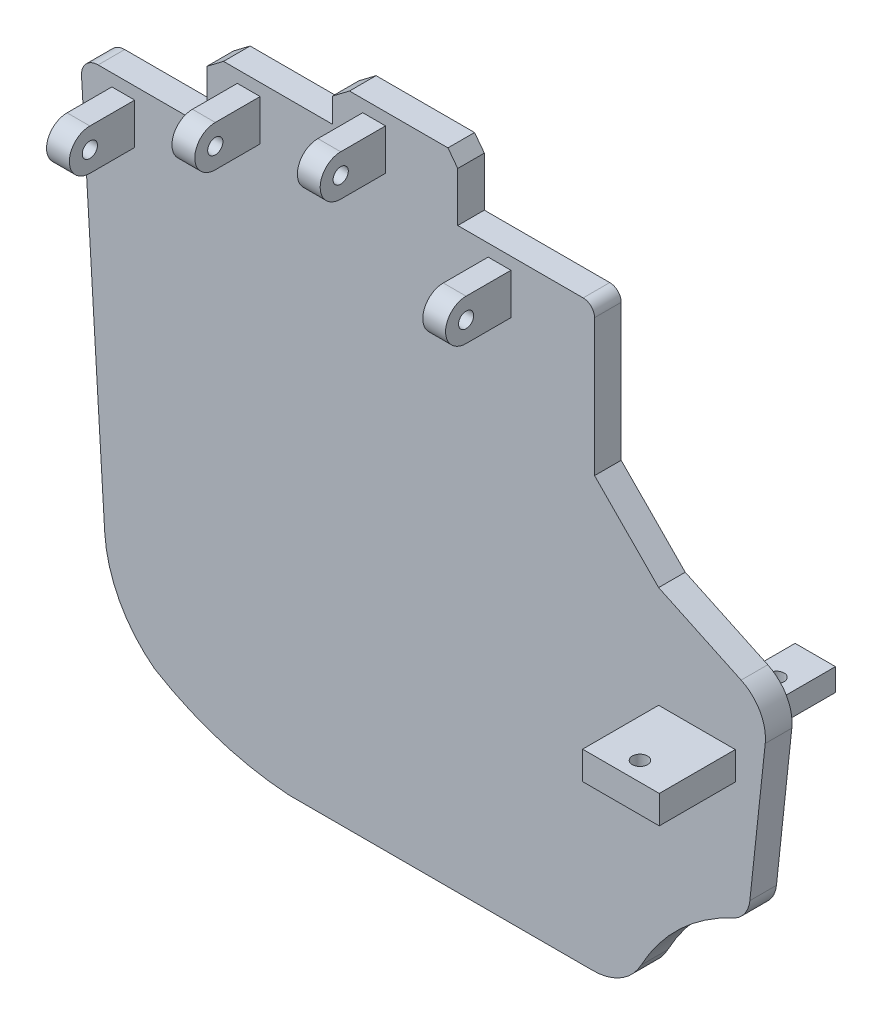
SolidWorks part; units mm, degrees
ref_plane "Front Plane" through (0, 0, 0) normal (0, 0, 1) x (1, 0, 0)
ref_plane "Top Plane" through (0, 0, 0) normal (0, 1, 0) x (1, 0, 0)
ref_plane "Right Plane" through (0, 0, 0) normal (1, 0, 0) x (0, 0, -1)
sketch "Sketch1" plane through (0, 0, 0) normal (0, 0, 1) x (1, 0, 0)
  line L0 (0, 0) -> (40, 0)
  line L1 (60.6551, 18.2857) -> (62.676, 37.2057)
  line L2 (59.5073, 42.8438) -> (48.6521, 47.9589)
  line L3 (48.6521, 47.9589) -> (40.223, 56.5)
  line L4 (40.223, 56.5) -> (40.223, 74.5)
  line L5 (38.723, 76) -> (22.223, 76)
  line L6 (22.223, 76) -> (22.223, 82.5)
  line L7 (22.223, 82.5) -> (20.934, 84.2022)
  line L8 (20.934, 84.2022) -> (7.9777, 84.2022)
  line L9 (7.9777, 84.2022) -> (5.723, 82.4947)
  line L10 (5.723, 82.4947) -> (5.723, 79.2947)
  line L11 (5.723, 79.2947) -> (-8.5938, 79.2947)
  line L12 (-8.5938, 79.2947) -> (-10.777, 77.6413)
  line L13 (-10.777, 77.6413) -> (-10.777, 70.6413)
  line L14 (-10.777, 70.6413) -> (-25.0938, 70.6413)
  line L15 (-27.277, 68.3221) -> (-24.2226, 17.8235)
  arc A0 (40, 0) -> (46.3551, 3.8023) centre (40, 7.2121) ccw
  arc A1 (46.3551, 3.8023) -> (58.452, 15.2105) centre (69.4891, -8.6104) cw
  arc A2 (58.452, 15.2105) -> (60.6551, 18.2857) centre (56.8383, 18.6934) ccw
  arc A3 (62.676, 37.2057) -> (59.5073, 42.8438) centre (57.1298, 37.7981) ccw
  arc A4 (40.223, 74.5) -> (38.723, 76) centre (38.723, 74.5) ccw
  arc A5 (-25.0938, 70.6413) -> (-27.277, 68.3221) centre (-25.0938, 68.4541) ccw
  arc A6 (-24.2226, 17.8235) -> (-17.6447, 5.5352) centre (-7.5746, 18.8305) ccw
  arc A7 (-17.6447, 5.5352) -> (0, 0) centre (2.5612, 39.0552) ccw
  dimension "D1" = 76
  dimension "D2" = 40
  dimension "D3" = 16.5
  dimension "D4" = 7
  dimension "D5" = 18
  dimension "D6" = 6.5
  dimension "D7" = 3.2
  dimension "D8" = 16.5
  dimension "D9" = 16.5
  dimension "D10" = 16.5
  dimension "D11" = 67.5
  dimension "D12" = 12
  dimension "D13" = 12
extrude "Boss-Extrude1" add sketch "Sketch1" along normal blind 3.5
sketch "Sketch2" plane through (0, 0, 3.5) normal (0, 0, 1) x (1, 0, 0)
  line L0 (-23.277, 69.0413) -> (-20.277, 69.0413)
  line L1 (-20.277, 69.0413) -> (-20.277, 63.6413)
  line L2 (-20.277, 63.6413) -> (-23.277, 63.6413)
  line L3 (-23.277, 63.6413) -> (-23.277, 69.0413)
  line L4 (-10.777, 77.6413) -> (-10.777, 70.6413) construction
  line L5 (-10.777, 70.6413) -> (-25.0938, 70.6413) construction
  line L6 (5.723, 79.2947) -> (-8.5938, 79.2947) construction
  line L7 (-6.777, 77.6947) -> (-3.777, 77.6947)
  line L8 (-6.777, 77.6947) -> (-6.777, 72.2947)
  line L9 (-6.777, 72.2947) -> (-3.777, 72.2947)
  line L10 (-3.777, 77.6947) -> (-3.777, 72.2947)
  line L11 (9.723, 82.6022) -> (12.723, 82.6022)
  line L12 (9.723, 82.6022) -> (9.723, 77.2022)
  line L13 (9.723, 77.2022) -> (12.723, 77.2022)
  line L14 (12.723, 82.6022) -> (12.723, 77.2022)
  line L15 (26.223, 74.4) -> (29.223, 74.4)
  line L16 (26.223, 74.4) -> (26.223, 69)
  line L17 (26.223, 69) -> (29.223, 69)
  line L18 (29.223, 74.4) -> (29.223, 69)
  line L19 (20.934, 84.2022) -> (7.9777, 84.2022) construction
  line L20 (38.723, 76) -> (22.223, 76) construction
  line L21 (5.723, 82.4947) -> (5.723, 79.2947) construction
  line L22 (22.223, 76) -> (22.223, 82.5) construction
  point P26 (-3.777, 74.9947)
  dimension "D1" = 3
  dimension "D2" = 5.4
  dimension "D3" = 9.5
  dimension "D4" = 1.6
  dimension "D5" = 1.6
  dimension "D6" = 1.6
  dimension "D7" = 1.6
  dimension "D8" = 9.5
  dimension "D9" = 9.5
  dimension "D10" = 9.5
extrude "Boss-Extrude2" add sketch "Sketch2" along normal blind 8.6 separate body
fillet "Fillet1" 2 edges at (-21.777, 69.0413, 12.1) (-21.777, 63.6413, 12.1) type full round first side face at (-21.777, 69.0413, 7.8) second side face at (-21.777, 63.6413, 7.8) middle face at (-21.777, 66.3413, 12.1)
sketch "Sketch3" plane through (-23.277, 0, 0) normal (-1, 0, 0) x (0, 0, 1)
  circle A0 centre (9.4, 66.3413) radius 1
  dimension "D1" = 2
extrude "Cut-Extrude1" cut sketch "Sketch3" against normal blind 8.6
fillet "Fillet2" 2 edges at (-5.277, 77.6947, 12.1) (-5.277, 72.2947, 12.1) type full round first side face at (-5.277, 77.6947, 7.8) second side face at (-5.277, 72.2947, 7.8) middle face at (-5.277, 74.9947, 12.1)
fillet "Fillet3" 2 edges at (11.223, 82.6022, 12.1) (11.223, 77.2022, 12.1) type full round first side face at (11.223, 82.6022, 7.8) second side face at (11.223, 77.2022, 7.8) middle face at (11.223, 79.9022, 12.1)
fillet "Fillet4" 2 edges at (27.723, 69, 12.1) (27.723, 74.4, 12.1) type full round first side face at (27.723, 69, 7.8) second side face at (27.723, 74.4, 7.8) middle face at (27.723, 71.7, 12.1)
sketch "Sketch4" plane through (-6.777, 0, 0) normal (-1, 0, 0) x (0, 0, 1)
  circle A0 centre (9.4, 74.9947) radius 1
  dimension "D1" = 2
extrude "Cut-Extrude2" cut sketch "Sketch4" against normal blind 8.6
sketch "Sketch5" plane through (9.723, 0, 0) normal (-1, 0, 0) x (0, 0, 1)
  circle A0 centre (9.4, 79.9022) radius 1
  dimension "D1" = 2
extrude "Cut-Extrude3" cut sketch "Sketch5" against normal blind 8.6
sketch "Sketch6" plane through (26.223, 0, 0) normal (-1, 0, 0) x (0, 0, 1)
  circle A0 centre (9.4, 71.7) radius 1
  dimension "D1" = 2
extrude "Cut-Extrude4" cut sketch "Sketch6" against normal blind 8.6
sketch "Sketch7" plane through (0, 0, 3.5) normal (0, 0, 1) x (1, 0, 0)
  line L0 (48.65, 34.5489) -> (48.65, 30.8499)
  line L1 (48.65, 30.8499) -> (58.738, 30.8499)
  line L2 (58.738, 30.8499) -> (58.738, 34.5489)
  line L3 (58.738, 34.5489) -> (48.65, 34.5489)
extrude "Boss-Extrude3" add sketch "Sketch7" along normal blind 10
sketch "Sketch9" plane through (0, 0, 0) normal (0, 0, -1) x (-1, 0, 0)
  line L0 (-58.4158, 37.087) -> (-58.4158, 34.1376)
  line L1 (-58.4158, 34.1376) -> (-53.1067, 34.1376)
  line L2 (-53.1067, 34.1376) -> (-53.1067, 37.087)
  line L3 (-53.1067, 37.087) -> (-58.4158, 37.087)
extrude "Boss-Extrude4" add sketch "Sketch9" along normal blind 10
sketch "Sketch10" plane through (0, 37.087, 0) normal (0, 1, 0) x (1, 0, 0)
  line L0 (53.1067, 10) -> (58.4158, 10) construction
  line L2 (53.1067, 0) -> (58.4158, 0) construction
  circle A0 centre (55.7612, 4.9) radius 1
  point P2 (55.7612, 10)
  point P3 (58.1144, 4.9)
  dimension "D1" = 2
  dimension "D2" = 4.9
extrude "Cut-Extrude5" cut sketch "Sketch10" against normal through all
sketch "Sketch11" plane through (0, 34.5489, 0) normal (0, 1, 0) x (1, 0, 0)
  line L1 (58.738, -13.5) -> (48.65, -13.5) construction
  line L2 (58.738, -3.5) -> (48.65, -3.5) construction
  circle A0 centre (53.694, -11) radius 1
  point P5 (53.694, -13.5)
  point P6 (53.694, -3.5)
  dimension "D1" = 2
  dimension "D2" = 7.5
extrude "Cut-Extrude6" cut sketch "Sketch11" against normal blind 36
